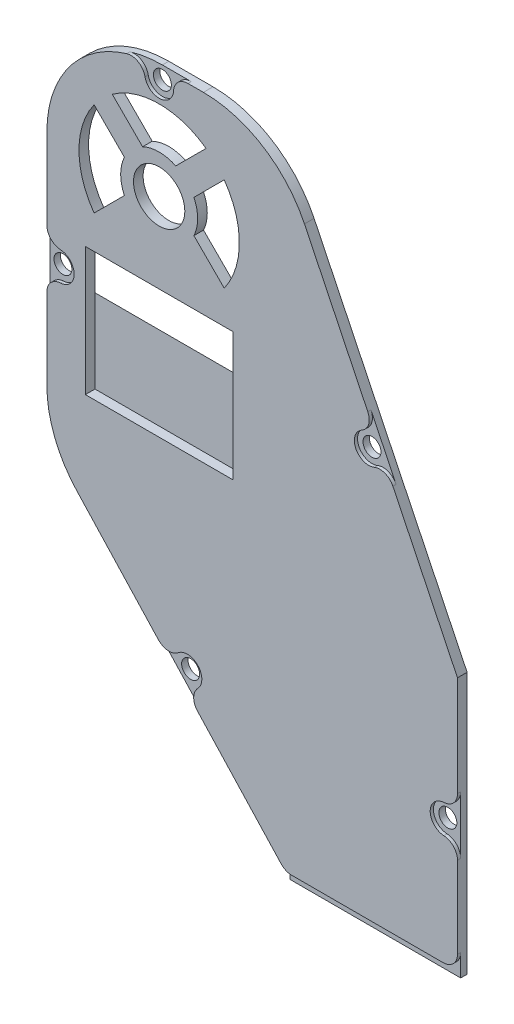
SolidWorks part; units mm, degrees
ref_plane "정면" through (0, 0, 0) normal (0, 0, 1) x (1, 0, 0)
ref_plane "윗면" through (0, 0, 0) normal (0, 1, 0) x (1, 0, 0)
ref_plane "우측면" through (0, 0, 0) normal (1, 0, 0) x (0, 0, -1)
sketch "스케치1" plane through (0, 0, 0) normal (0, 0, 1) x (1, 0, 0)
  line L0 (46.5, -82.5) -> (46.5, -41.729)
  line L1 (-12.8467, -46.139) -> (19.8622, -81.5)
  line L2 (-17.5, 0) -> (-17.5, -34.2557)
  line L3 (6.8941, 17.5) -> (0, 17.5)
  line L4 (46.5, -41.729) -> (22.6502, 7.6155)
  line L5 (19.8622, -81.5) -> (19.8622, -82.5)
  line L17 (19.8622, -82.5) -> (46.5, -82.5)
  arc A0 (-17.5, -34.2557) -> (-12.8467, -46.139) centre (0, -34.2557) ccw
  arc A1 (0, 17.5) -> (-17.5, 0) centre (0, 0) ccw
  arc A2 (22.6502, 7.6155) -> (6.8941, 17.5) centre (6.8941, 0) ccw
extrude "보스-돌출1" add sketch "스케치1" along normal blind 1
sketch "스케치2" plane through (0, 0, 1) normal (0, 0, -1) x (-1, 0, 0)
  line L0 (-19.8622, -82.5) -> (-46.5, -82.5) construction
  line L5 (-46.5, -82.5) -> (-46.5, -41.729) construction
  line L6 (12.8467, -46.139) -> (-19.8622, -81.5) construction
  line L14 (-21.6616, -80.5) -> (11.3785, -44.7809)
  line L15 (15.5, -34.2557) -> (15.5, 0)
  line L16 (0, 15.5) -> (-6.8941, 15.5)
  line L17 (-20.8495, 6.7451) -> (-44.5, -42.187)
  line L18 (-44.5, -42.187) -> (-44.5, -80.5)
  line L19 (-44.5, -80.5) -> (-21.6616, -80.5)
  line L20 (-21.6616, -80.5) -> (11.3785, -44.7809) construction
  line L21 (15.5, -34.2557) -> (15.5, 0) construction
  line L22 (0, 15.5) -> (-6.8941, 15.5) construction
  line L23 (-20.8495, 6.7451) -> (-44.5, -42.187) construction
  line L24 (-44.5, -42.187) -> (-44.5, -80.5) construction
  line L25 (-44.5, -80.5) -> (-21.6616, -80.5) construction
  line L26 (-46.5, -81.3) -> (-19.6772, -81.3)
  line L61 (-33.6539, -19.7467) -> (-35.4546, -18.8764)
  line L62 (-31.6956, -15.6951) -> (-33.4963, -14.8248)
  line L63 (-33.4963, -14.8248) -> (-22.6502, 7.6155)
  line L64 (-2.25, 15.5) -> (-2.25, 17.5)
  line L65 (2.25, 15.5) -> (2.25, 17.3548)
  line L66 (-6.8941, 17.5) -> (0, 17.5)
  line L67 (-46.5, -41.729) -> (-22.6502, 7.6155)
  line L68 (17.5, 0) -> (17.5, -34.2557)
  line L69 (12.8467, -46.139) -> (-19.8622, -81.5)
  line L70 (-46.5, -82.5) -> (-46.5, -41.729)
  line L71 (-6.8941, 17.5) -> (-2.25, 17.5)
  line L72 (-46.5, -41.729) -> (-35.4546, -18.8764)
  line L73 (17.5, 0) -> (17.5, -14.8779)
  line L74 (12.8467, -46.139) -> (-1.4043, -61.5456)
  line L75 (-46.5, -81.3) -> (-46.5, -64.11)
  line L76 (15.5, -14.8779) -> (17.5, -14.8779)
  line L77 (15.5, -19.3779) -> (17.5, -19.3779)
  line L78 (17.5, -19.3779) -> (17.5, -34.2557)
  line L79 (-2.8725, -60.1875) -> (-1.4043, -61.5456)
  line L80 (-5.9282, -63.4909) -> (-4.46, -64.849)
  line L81 (-4.46, -64.849) -> (-19.6772, -81.3)
  line L82 (-44.5, -59.61) -> (-46.5, -59.61)
  line L83 (-44.5, -64.11) -> (-46.5, -64.11)
  line L84 (-46.5, -59.61) -> (-46.5, -41.729)
  arc A3 (-33.6539, -19.7467) -> (-31.6956, -15.6951) centre (-32.6747, -17.7209) ccw
  arc A4 (15.5, -14.8779) -> (15.5, -19.3779) centre (15.5, -17.1279) ccw
  arc A5 (-2.8725, -60.1875) -> (-5.9282, -63.4909) centre (-4.4004, -61.8392) ccw
  arc A6 (11.3785, -44.7809) -> (15.5, -34.2557) centre (0, -34.2557) ccw
  arc A7 (15.5, 0) -> (0, 15.5) centre (0, 0) ccw
  arc A8 (-6.8941, 15.5) -> (-20.8495, 6.7451) centre (-6.8941, 0) ccw
  arc A9 (11.3785, -44.7809) -> (15.5, -34.2557) centre (0, -34.2557) ccw construction
  arc A10 (15.5, 0) -> (0, 15.5) centre (0, 0) ccw construction
  arc A11 (-6.8941, 15.5) -> (-20.8495, 6.7451) centre (-6.8941, 0) ccw construction
  arc A12 (-2.25, 15.5) -> (2.25, 15.5) centre (0, 15.5) ccw
  arc A13 (-44.5, -64.11) -> (-44.5, -59.61) centre (-44.5, -61.86) ccw
  arc A29 (17.5, 0) -> (0, 17.5) centre (0, 0) ccw
  arc A30 (-6.8941, 17.5) -> (-22.6502, 7.6155) centre (-6.8941, 0) ccw
  arc A31 (12.8467, -46.139) -> (17.5, -34.2557) centre (0, -34.2557) ccw
  arc A32 (17.5, 0) -> (2.25, 17.3548) centre (0, 0) ccw
  arc A33 (-6.8941, 17.5) -> (-22.6502, 7.6155) centre (-6.8941, 0) ccw
  arc A34 (12.8467, -46.139) -> (17.5, -34.2557) centre (0, -34.2557) ccw
  point P10 (0, 0)
  point P11 (0, 0)
  point P18 (-46.5, -81.3)
  point P22 (-19.6772, -81.3)
  dimension "D2" = 4.5
  dimension "D6" = 25.42
  dimension "D3" = 19.44
  dimension "D5" = 1.2
  dimension "D1" = 2
  dimension "D9" = 0
extrude "보스-돌출2" add sketch "스케치2" against normal blind 0.5
fillet "필렛1" radius 2.25 12 edges at (-17.5, -14.8779, 1.25) (-17.5, -19.3779, 1.25) (2.25, 17.5, 1.25) (-2.25, 17.3548, 1.25) (35.4546, -18.8764, 1.25) (33.4963, -14.8248, 1.25) (46.5, -64.11, 1.25) (46.5, -59.61, 1.25) (1.4043, -61.5456, 1.25) (4.46, -64.849, 1.25) (19.6772, -81.3, 1.25) (46.5, -81.3, 1.25)
sketch "스케치3" plane through (0, 0, 0) normal (0, 0, -1) x (-1, 0, 0)
  circle A0 centre (0, 15.5) radius 1.4
  circle A1 centre (15.5, -17.1279) radius 1.4
  circle A2 centre (-32.6747, -17.7209) radius 1.4
  circle A3 centre (-44.5, -61.86) radius 1.4
  circle A4 centre (-4.4004, -61.8392) radius 1.4
  dimension "D1" = 2.8
extrude "컷-돌출1" cut sketch "스케치3" against normal up to next
sketch "스케치4" plane through (0, 0, 1.5) normal (0, 0, 1) x (1, 0, 0)
  line L0 (4.4931, 17.5) -> (6.8941, 17.5) construction
  line L1 (-11.5, -12.5) -> (11.5, -12.5)
  line L2 (-11.5, -12.5) -> (-11.5, -32.5)
  line L3 (-11.5, -32.5) -> (11.5, -32.5)
  line L4 (11.5, -12.5) -> (11.5, -32.5)
  line L16 (-5.4142, -2.5858) -> (-10.1392, -7.3108)
  line L27 (5.4142, -2.5858) -> (10.1392, -7.3108)
  line L30 (5.4142, 2.5858) -> (10.1392, 7.3108)
  line L34 (2.5858, 5.4142) -> (7.3108, 10.1392)
  line L37 (-2.5858, 5.4142) -> (-7.3108, 10.1392)
  line L41 (-5.4142, 2.5858) -> (-10.1392, 7.3108)
  circle A0 centre (0, 0) radius 4
  arc A1 (10.1392, -7.3108) -> (10.1392, 7.3108) centre (0, 0) ccw
  arc A2 (-5.4142, 2.5858) -> (-5.4142, -2.5858) centre (0, 0) ccw
  arc A3 (2.5858, 5.4142) -> (-2.5858, 5.4142) centre (0, 0) ccw
  arc A4 (5.4142, -2.5858) -> (5.4142, 2.5858) centre (0, 0) ccw
  arc A6 (-10.1392, 7.3108) -> (-10.1392, -7.3108) centre (0, 0) ccw
  arc A7 (7.3108, 10.1392) -> (-7.3108, 10.1392) centre (0, 0) ccw
  point P15 (0, -12.5)
  dimension "D1" = 8
  dimension "D2" = 12
  dimension "D3" = 25
  dimension "D4" = 20
  dimension "D5" = 30
  dimension "D6" = 23
extrude "컷-돌출2" cut sketch "스케치4" against normal up to next
sketch "스케치6" plane through (0, 0, 0) normal (0, 0, -1) x (-1, 0, 0)
  line L0 (17.5, 0) -> (17.5, -34.2557) construction
  line L1 (17.5, -19.5) -> (-17.5, -19.5)
  line L2 (17.5, -19.5) -> (17.5, -34.2557)
  line L3 (16.9775, -38.5) -> (-17.5, -38.5)
  line L4 (-17.5, -19.5) -> (-17.5, -38.5)
  line L5 (11.5, -12.5) -> (-11.5, -12.5) construction
  line L6 (-11.5, -12.5) -> (-11.5, -32.5) construction
  line L7 (-11.5, -32.5) -> (11.5, -32.5) construction
  arc A2 (12.8467, -46.139) -> (17.5, -34.2557) centre (0, -34.2557) ccw
  arc A3 (16.9775, -38.5) -> (17.5, -34.2557) centre (0, -34.2557) ccw
  dimension "D1" = 7
  dimension "D2" = 6
  dimension "D3" = 6
  dimension "D4" = 0
extrude "보스-돌출3" add sketch "스케치6" along normal blind 1.5
fillet "필렛2" radius 5 3 edges at (0, -19.5, -1.5) (17.5, -29, -1.5) (0.2612, -38.5, -1.5)
